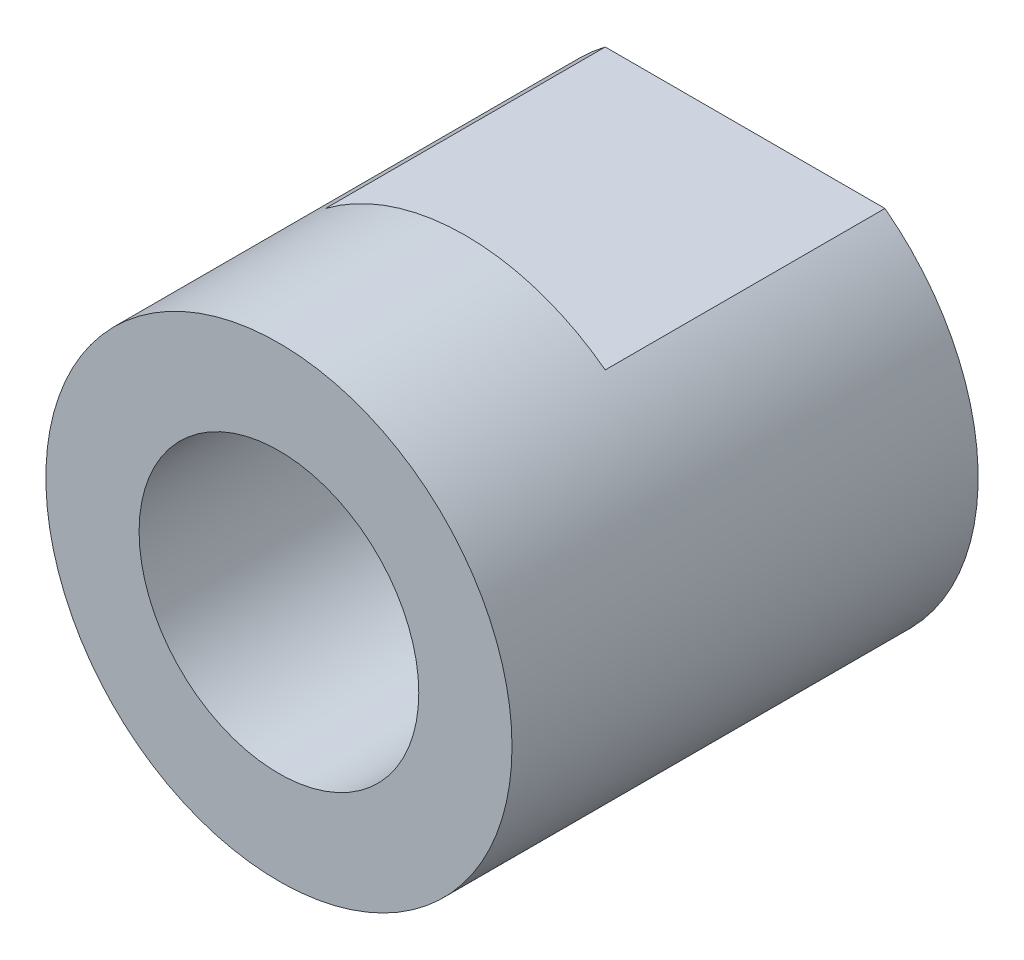
SolidWorks part; units mm, degrees
ref_plane "Plan de face" through (0, 0, 0) normal (0, 0, 1) x (1, 0, 0)
ref_plane "Plan de dessus" through (0, 0, 0) normal (0, 1, 0) x (1, 0, 0)
ref_plane "Plan de droite" through (0, 0, 0) normal (1, 0, 0) x (0, 0, -1)
sketch "Esquisse1" plane through (0, 0, 0) normal (0, 0, 1) x (1, 0, 0)
  circle A0 centre (0, 0) radius 5
  dimension "D1" = 10
extrude "Boss.-Extru.1" add sketch "Esquisse1" along normal blind 10
sketch "Esquisse2" plane through (0, 0, 10) normal (0, 0, 1) x (1, 0, 0)
  circle A0 centre (0, 0) radius 3
  dimension "D1" = 6
extrude "Enlèv. mat.-Extru.1" cut sketch "Esquisse2" against normal blind 10
sketch "Esquisse3" plane through (0, 0, 0) normal (1, 0, 0) x (0, 0, -1)
  line L0 (0, 0) -> (-2.7108, 0) construction
  line L1 (0, 5) -> (-6, 5)
  line L2 (0, 5) -> (0, 4)
  line L3 (0, 4) -> (-6, 4)
  line L4 (-6, 5) -> (-6, 4)
  line L5 (0, -4) -> (-6, -4)
  line L6 (-6, -5) -> (-6, -4)
  line L7 (0, -5) -> (-6, -5)
  line L8 (0, -5) -> (0, -4)
  dimension "D1" = 4
  dimension "D2" = 6
extrude "Enlèv. mat.-Extru.2" cut sketch "Esquisse3" against normal blind 10 and the other way blind 10
